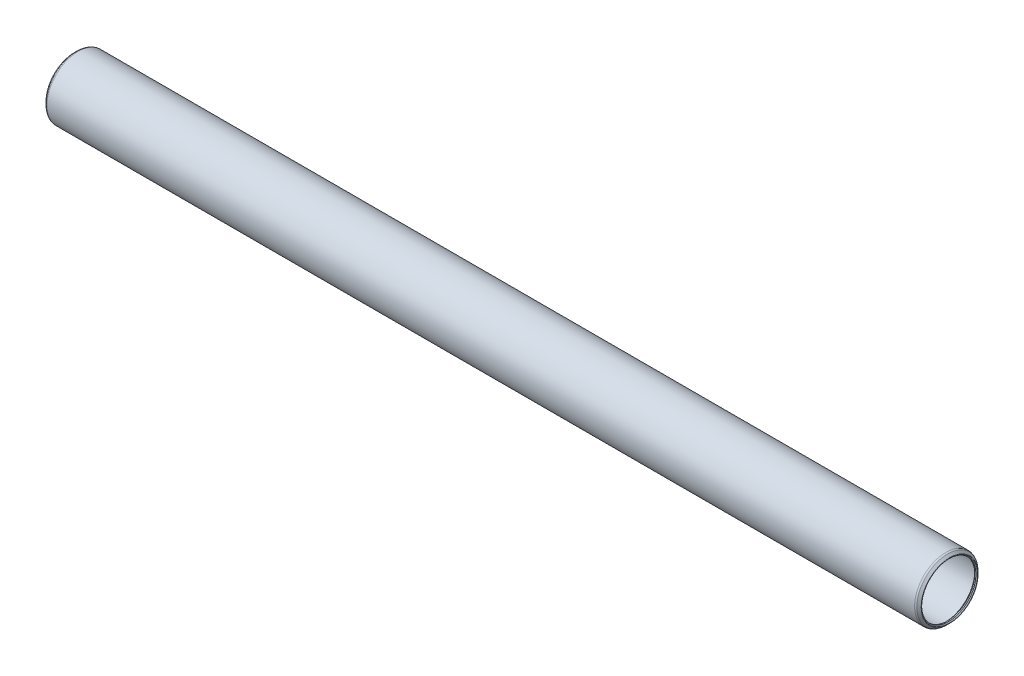
SolidWorks part; units mm, degrees
material "AISI 304"
ref_plane "Front Plane" through (0, 0, 0) normal (0, 0, 1) x (1, 0, 0)
ref_plane "Top Plane" through (0, 0, 0) normal (0, 1, 0) x (1, 0, 0)
ref_plane "Right Plane" through (0, 0, 0) normal (1, 0, 0) x (0, 0, -1)
ref_plane "Plane1" through (285.8897, 0, 0) normal (1, 0, 0) x (0, 0, -1)
sketch "Sketch1" plane through (0, 0, 0) normal (0, 0, 1) x (1, 0, 0)
  line L0 (-0.6395, 9.1676) -> (-0.381, 8.9091)
  line L1 (-0.381, 8.9091) -> (0, 8.9091)
  line L2 (0, 8.9091) -> (0.762, 9.671)
  line L3 (0.762, 9.671) -> (285.1277, 9.671)
  line L4 (285.1277, 9.671) -> (285.8897, 8.9091)
  line L5 (285.8897, 8.9091) -> (286.2707, 8.9091)
  line L6 (286.2707, 8.9091) -> (286.5292, 9.1676)
  line L7 (286.5292, 9.3472) -> (285.8443, 10.0321)
  line L8 (285.3055, 10.2553) -> (0.5842, 10.2553)
  line L9 (0.0454, 10.0321) -> (-0.6395, 9.3472)
  line L10 (285.8897, 0) -> (0, 0) construction
  arc A0 (-0.6395, 9.3472) -> (-0.6395, 9.1676) centre (-0.5497, 9.2574) ccw
  arc A1 (286.5292, 9.1676) -> (286.5292, 9.3472) centre (286.4394, 9.2574) ccw
  arc A2 (285.8443, 10.0321) -> (285.3055, 10.2553) centre (285.3055, 9.4933) ccw
  arc A3 (0.5842, 10.2553) -> (0.0454, 10.0321) centre (0.5842, 9.4933) ccw
revolve "Revolve1" add sketch "Sketch1" angle 360 about L10 reverse direction yes
ref_plane "Plane2" through (142.9449, 0, 0) normal (1, 0, 0) x (0, 0, -1)
ref_plane "cp1 XY" through (142.9449, 0, 0) normal (1, 0, 0) x (0, 0, -1)
ref_plane "cp1 XZ" through (0, 10.2553, 0) normal (0, -1, 0) x (-1, 0, 0)
ref_plane "cp1 YZ" through (0, 0, 0) normal (0, 0, -1) x (-1, 0, 0)
ref_axis "cp1 X" through (142.9449, 10.2553, 80.9) along (0, 0, -1)
ref_axis "cp1 Y" through (142.9449, -50, 0) along (0, 1, 0)
ref_axis "cp1 Z" through (80.9, 10.2553, 0) along (-1, 0, 0)
sketch3d "cp1"
  point P0 (142.9449, 10.2553, 0)
ref_plane "cp2 XY" through (142.9449, 0, 0) normal (1, 0, 0) x (0, 0, -1)
ref_plane "cp2 XZ" through (0, 0, 0) normal (0, -1, 0) x (-1, 0, 0)
ref_plane "cp2 YZ" through (0, 0, -10.2553) normal (0, 0, -1) x (-1, 0, 0)
ref_axis "cp2 X" through (142.9449, 0, 80.9) along (0, 0, -1)
ref_axis "cp2 Y" through (142.9449, -50, -10.2553) along (0, 1, 0)
ref_axis "cp2 Z" through (80.9, 0, -10.2553) along (-1, 0, 0)
sketch3d "cp2"
  point P0 (142.9449, 0, -10.2553)
ref_plane "cp3 XY" through (142.9449, 0, 0) normal (1, 0, 0) x (0, 0, -1)
ref_plane "cp3 XZ" through (0, -10.2553, 0) normal (0, -1, 0) x (-1, 0, 0)
ref_plane "cp3 YZ" through (0, 0, 0) normal (0, 0, -1) x (-1, 0, 0)
ref_axis "cp3 X" through (142.9449, -10.2553, 80.9) along (0, 0, -1)
ref_axis "cp3 Y" through (142.9449, -50, 0) along (0, 1, 0)
ref_axis "cp3 Z" through (80.9, -10.2553, 0) along (-1, 0, 0)
sketch3d "cp3"
  point P0 (142.9449, -10.2553, 0)
ref_plane "cp4 XY" through (142.9449, 0, 0) normal (1, 0, 0) x (0, 0, -1)
ref_plane "cp4 XZ" through (0, 0, 0) normal (0, -1, 0) x (-1, 0, 0)
ref_plane "cp4 YZ" through (0, 0, 10.2553) normal (0, 0, -1) x (-1, 0, 0)
ref_axis "cp4 X" through (142.9449, 0, 80.9) along (0, 0, -1)
ref_axis "cp4 Y" through (142.9449, -50, 10.2553) along (0, 1, 0)
ref_axis "cp4 Z" through (80.9, 0, 10.2553) along (-1, 0, 0)
sketch3d "cp4"
  point P0 (142.9449, 0, 10.2553)
ref_plane "tube_front XY" through (0, 0, 0) normal (1, 0, 0) x (0, 0, -1)
ref_plane "tube_front XZ" through (0, 0, 0) normal (0, -1, 0) x (-1, 0, 0)
ref_plane "tube_front YZ" through (0, 0, 0) normal (0, 0, -1) x (-1, 0, 0)
ref_axis "tube_front X" through (0, 0, 80.9) along (0, 0, -1)
ref_axis "tube_front Y" through (0, -50, 0) along (0, 1, 0)
ref_axis "tube_front Z" through (80.9, 0, 0) along (-1, 0, 0)
sketch3d "tube_front"
  point P0 (0, 0, 0)
ref_plane "tube_rear XY" through (285.8897, 0, 0) normal (1, 0, 0) x (0, 0, -1)
ref_plane "tube_rear XZ" through (0, 0, 0) normal (0, -1, 0) x (-1, 0, 0)
ref_plane "tube_rear YZ" through (0, 0, 0) normal (0, 0, -1) x (-1, 0, 0)
ref_axis "tube_rear X" through (285.8897, 0, 80.9) along (0, 0, -1)
ref_axis "tube_rear Y" through (285.8897, -50, 0) along (0, 1, 0)
ref_axis "tube_rear Z" through (80.9, 0, 0) along (-1, 0, 0)
sketch3d "tube_rear"
  point P0 (285.8897, 0, 0)
